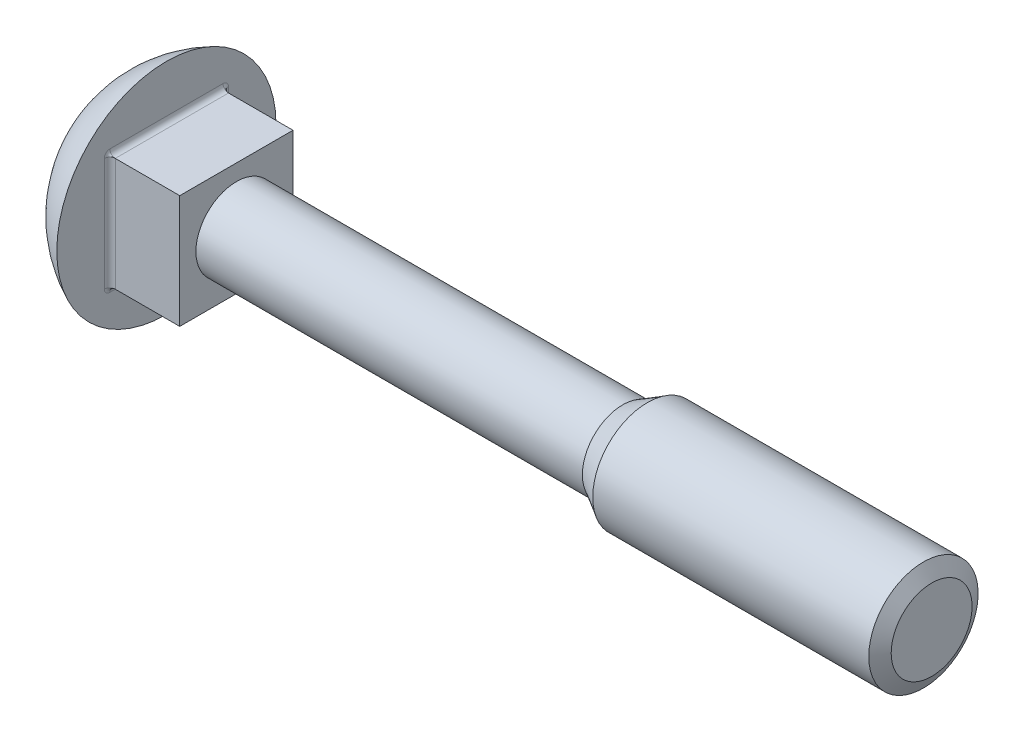
SolidWorks part; units mm, degrees
ref_plane "前视" through (0, 0, 0) normal (0, 0, 1) x (1, 0, 0)
ref_plane "上视" through (0, 0, 0) normal (0, 1, 0) x (1, 0, 0)
ref_plane "右视" through (0, 0, 0) normal (1, 0, 0) x (0, 0, -1)
sketch "尺寸草图" plane through (0, 0, 0) normal (0, 1, 0) x (1, 0, 0)
  line L0 (0, 0) -> (70, 0) construction
  point P3 (60, 0)
  point P4 (26, 0)
  point P5 (48.7, 0)
  point P6 (6.4, 0)
  point P7 (6.48, 0)
  point P8 (10.36, 0)
  point P9 (69.5, 0)
  point P10 (11, 0)
  point P11 (3.8, 0)
  point P12 (47.2, 0)
  dimension "b" = 26
  dimension "K1" = 6.4
  dimension "K" = 6.48
  dimension "Ss" = 10.36
  dimension "R" = 11
  dimension "X" = 3.8
  dimension "dk" = 21.3
  dimension "r_" = 0.5
  dimension "l" = 70
  dimension "d" = 10
  dimension "P" = 1.5
sketch "草图1" plane through (0, 0, 0) normal (0, 0, 1) x (1, 0, 0)
  line L0 (0, 0) -> (90.9034, 0) construction
  line L1 (6.48, 10.0284) -> (6.48, 0)
  line L2 (6.48, 0) -> (0, 0)
  arc A0 (0, 0) -> (6.48, 10.0284) centre (11, 0) cw
  dimension "D1" = 11
  dimension "D2" = 6.48
revolve "基体-旋转" add sketch "草图1" angle 360 about L0
sketch "草图2" plane through (6.48, 0, 0) normal (1, 0, 0) x (0, 0, -1)
  line L0 (5.18, 5.18) -> (-5.18, -5.18) construction
  line L1 (-5.18, 5.18) -> (5.18, 5.18)
  line L2 (-5.18, 5.18) -> (-5.18, -5.18)
  line L3 (-5.18, -5.18) -> (5.18, -5.18)
  line L4 (5.18, 5.18) -> (5.18, -5.18)
  dimension "D1" = 10.36
extrude "凸台-拉伸1" add sketch "草图2" along normal blind 6.4
fillet "圆角1" radius 0.5 4 edges at (6.48, 5.18, 0) (6.48, 0, -5.18) (6.48, -5.18, 0) (6.48, 0, 5.18)
sketch "草图3" plane through (0, 0, 0) normal (0, 1, 0) x (1, 0, 0)
  line L0 (12.88, 3.701) -> (48.2301, 3.701)
  line L1 (12.88, 5.18) -> (12.88, -5.18) construction
  line L2 (48.2301, 3.701) -> (50.48, 5)
  line L3 (50.48, 5) -> (76.48, 5)
  line L4 (76.48, 5) -> (76.48, 0)
  line L5 (0, 0) -> (76.48, 0) construction
  line L6 (12.88, 0) -> (76.48, 0)
  line L7 (12.88, 3.701) -> (12.88, 0)
  line L8 (6.48, -10.0284) -> (6.48, 10.0284) construction
  dimension "D1" = 26
  dimension "D2" = 2.2499
  dimension "D3" = 70
  dimension "D4" = 5
  dimension "D5" = 3.701
  dimension "D6" = 150
revolve "凸台-旋转1" add sketch "草图3" angle 360 about L5
cosmetic thread "螺纹线1" parameters "D1"=27.125, "D2"=7.402
sketch "草图4" plane through (0, 0, 0) normal (0, 1, 0) x (1, 0, 0)
  line L0 (75.73, 5) -> (76.48, 3.701)
  line L1 (76.48, -5) -> (76.48, 5) construction
  line L2 (76.48, 3.701) -> (77.23, 5)
  line L3 (77.23, 5) -> (75.73, 5)
  line L5 (0, 0) -> (13.7241, 0) construction
  line L6 (0, 0) -> (90.9034, 0) construction
  line L7 (50.48, 5) -> (76.48, 5) construction
  dimension "D1" = 60
  dimension "D2" = 60
  dimension "D3" = 1.299
revolve "切除-旋转1" cut sketch "草图4" angle 360 about L5
pattern_linear "阵列(线性)1" [suppressed] count 18 spacing 1.5
